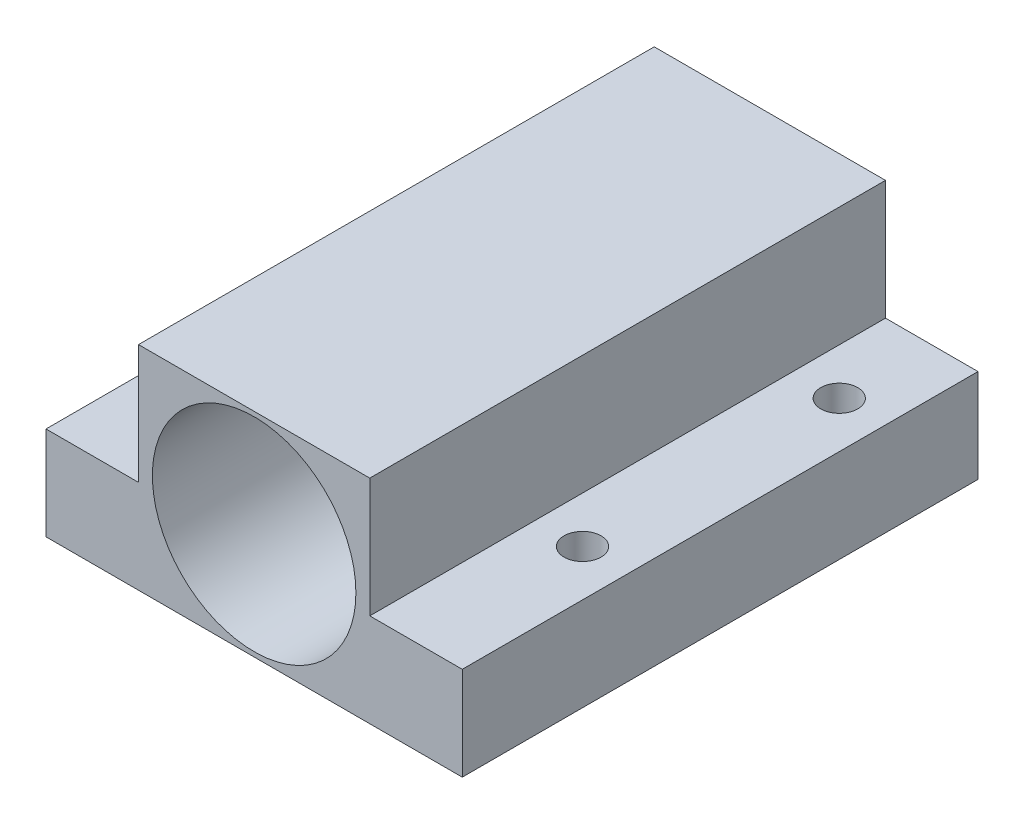
SolidWorks part; units mm, degrees
material "ABS"
ref_plane "Front Plane" through (0, 0, 0) normal (0, 0, 1) x (1, 0, 0)
ref_plane "Top Plane" through (0, 0, 0) normal (0, 1, 0) x (1, 0, 0)
ref_plane "Right Plane" through (0, 0, 0) normal (1, 0, 0) x (0, 0, -1)
sketch "Sketch1" plane through (0, 0, 0) normal (0, 0, 1) x (1, 0, 0)
  line L0 (-65.4098, -16.7) -> (184.5902, -16.7) construction
  line L1 (-12.5, 6.3) -> (12.5, 6.3)
  line L2 (-12.5, 6.3) -> (-12.5, -16.7)
  line L3 (-12.5, -16.7) -> (12.5, -16.7)
  line L4 (12.5, 6.3) -> (12.5, -16.7)
  line L5 (-12.5, 6.3) -> (12.5, -16.7) construction
  line L6 (-12.5, -16.7) -> (12.5, 6.3) construction
  line L7 (12.5, -16.7) -> (22.5, -16.7)
  line L8 (12.5, -16.7) -> (12.5, -6.6)
  line L9 (12.5, -6.6) -> (22.5, -6.6)
  line L10 (22.5, -16.7) -> (22.5, -6.6)
  line L11 (12.5, -16.7) -> (22.5, -6.6) construction
  line L12 (12.5, -6.6) -> (22.5, -16.7) construction
  line L13 (-12.5, -16.7) -> (-22.5, -16.7)
  line L14 (-12.5, -16.7) -> (-12.5, -6.6)
  line L15 (-12.5, -6.6) -> (-22.5, -6.6)
  line L16 (-22.5, -16.7) -> (-22.5, -6.6)
  line L17 (-12.5, -16.7) -> (-22.5, -6.6) construction
  line L18 (-12.5, -6.6) -> (-22.5, -16.7) construction
  circle A0 centre (0, -5.2) radius 4.1
  circle A1 centre (0, -5.2) radius 11
  point P8 (0, -5.2)
  point P14 (17.5, -11.65)
  point P16 (-17.5, -11.65)
  dimension "D4" = 8.2
  dimension "D5" = 22
  dimension "D11" = 11.5
  dimension "D2" = 0
  dimension "D3" = 25
  dimension "D6" = 10
  dimension "D8" = 10
  dimension "D9" = 10.1
  dimension "D10" = 12.5
  dimension "D12" = 11.5
  dimension "D13" = 5.2
extrude "Boss-Extrude1" add sketch "Sketch1" along normal up to surface (55.75 mm away) contours L4 L1 L2 L3 A1 | L16 L13 L2 L15 | L7 L10 L9 L4 region at (0, 5.9603, 0) region at (-17.5, -11.65, 0) region at (17.5, -11.65, 0)
sketch "Sketch2" plane through (0, -6.6, 0) normal (0, 1, 0) x (1, 0, 0)
  line L0 (-22.5, 0) -> (-12.5, -55.75)
  line L1 (-12.5, -55.75) -> (-22.5, -55.75)
  line L2 (-22.5, -55.75) -> (-12.5, 0)
  line L3 (12.5, 0) -> (22.5, -55.75)
  line L4 (22.5, -55.75) -> (22.5, 0)
  line L5 (22.5, 0) -> (12.5, -55.75)
  circle A0 centre (-17.5, -10) radius 2
  circle A1 centre (17.5, -10) radius 2
  circle A2 centre (17.5, -10) radius 2 construction
  circle A3 centre (-17.5, -10) radius 2 construction
  circle A4 centre (-17.5, -37.75) radius 2
  circle A5 centre (17.5, -37.75) radius 2
  circle A6 centre (17.5, -37.75) radius 2 construction
  circle A7 centre (-17.5, -37.75) radius 2 construction
  dimension "D1" = 4
  dimension "D2" = 4
extrude "Cut-Extrude1" cut sketch "Sketch2" against normal through all contours A0 | A4 | A1 | A5
